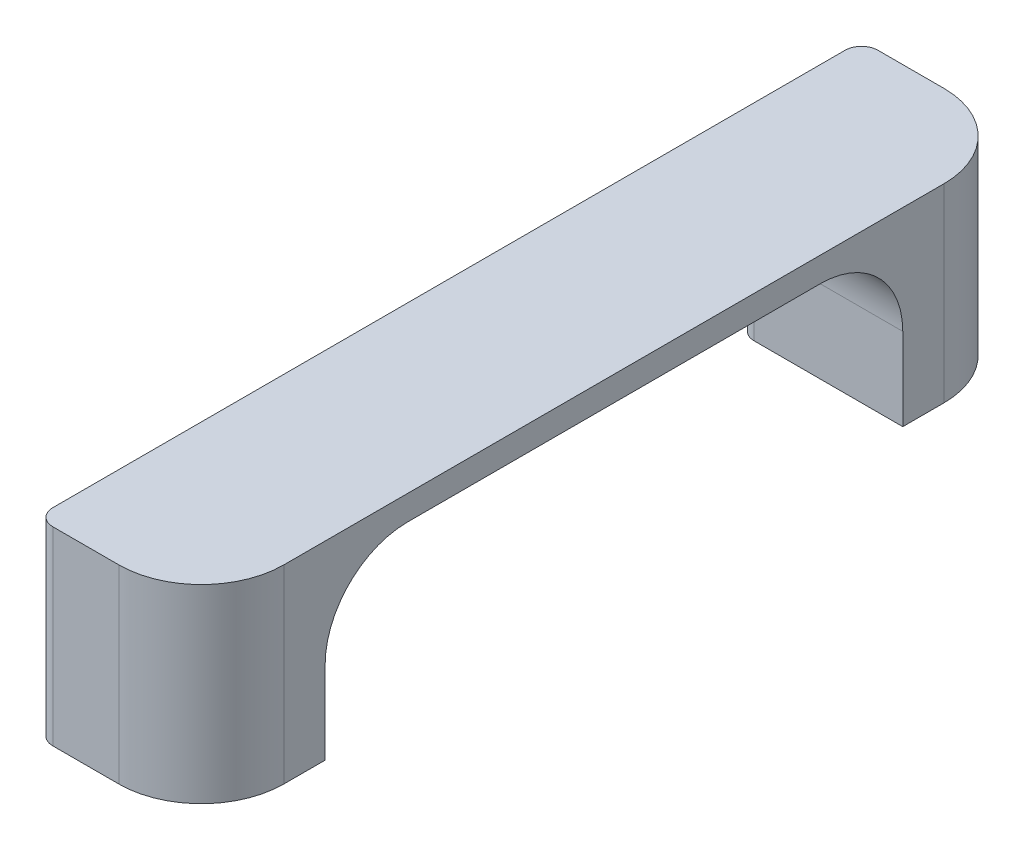
SolidWorks part; units mm, degrees
ref_plane "Alzado" through (0, 0, 0) normal (0, 0, 1) x (1, 0, 0)
ref_plane "Planta" through (0, 0, 0) normal (0, 1, 0) x (1, 0, 0)
ref_plane "Vista lateral" through (0, 0, 0) normal (1, 0, 0) x (0, 0, -1)
sketch "Croquis1" plane through (0, 0, 0) normal (0, 1, 0) x (1, 0, 0)
  line L1 (0, 0) -> (20, 0)
  line L2 (0, 0) -> (0, 90)
  line L3 (0, 90) -> (20, 90)
  line L4 (20, 0) -> (20, 90)
  dimension "D1" = 90
  dimension "D2" = 20
extrude "Saliente-Extruir1" add sketch "Croquis1" along normal blind 3
sketch "Croquis2" plane through (0, 0, 0) normal (0, -1, 0) x (1, 0, 0)
  line L0 (0, -90) -> (0, 0) construction
  line L1 (20, 0) -> (0, 0)
  line L2 (20, 0) -> (20, -10)
  line L3 (20, -10) -> (0, -10)
  line L4 (0, 0) -> (0, -10)
  line L5 (20, -90) -> (0, -90)
  line L6 (20, -90) -> (20, -80)
  line L7 (20, -80) -> (0, -80)
  line L8 (0, -90) -> (0, -80)
  line L9 (10, 0) -> (10, -90) construction
  dimension "D1" = 10
  dimension "D2" = 10
extrude "Saliente-Extruir2" add sketch "Croquis2" along normal blind 20
sketch "Croquis3" plane through (0, -20, 0) normal (0, -1, 0) x (1, 0, 0)
  line L0 (20, -5) -> (0, -5) construction
  line L1 (20, -10) -> (20, 0) construction
  line L2 (0, 0) -> (0, -10) construction
  line L8 (20, -85) -> (0, -85) construction
  line L9 (20, -90) -> (20, -80) construction
  line L10 (0, -80) -> (0, -90) construction
  circle A0 centre (12, -5) radius 2.1
  circle A1 centre (12, -85) radius 2.1
  dimension "D1" = 4.2
  dimension "D2" = 4.2
  dimension "D3" = 8
extrude "Cortar-Extruir1" cut sketch "Croquis3" against normal blind 4
sketch "Croquis4" plane through (0, 3, 0) normal (0, 1, 0) x (1, 0, 0)
  line L0 (0, 0) -> (20, 0) construction
  line L1 (20, 90) -> (0, 90)
  line L2 (20, 90) -> (20, 95)
  line L3 (20, 95) -> (0, 95)
  line L4 (0, 90) -> (0, 95)
  line L5 (0, 0) -> (20, 0)
  line L6 (0, 0) -> (0, -5)
  line L7 (0, -5) -> (20, -5)
  line L8 (20, 0) -> (20, -5)
  dimension "D1" = 5
  dimension "D2" = 5
extrude "Saliente-Extruir3" add sketch "Croquis4" against normal up to surface (23 mm away) up to face at (12, -20, -87.1)
fillet "Redondeo1" radius 10 2 edges at (20, -8.5, 5) (20, -8.5, -95)
fillet "Redondeo2" radius 2 4 edges at (0, -8.5, 5) (0, -10, -10) (0, -10, -80) (0, -8.5, -95)
fillet "Redondeo3" radius 10 4 edges at (0.5858, 0, -80.5858) (0.5858, 0, -9.4142) (11, 0, -80) (11, 0, -10)
